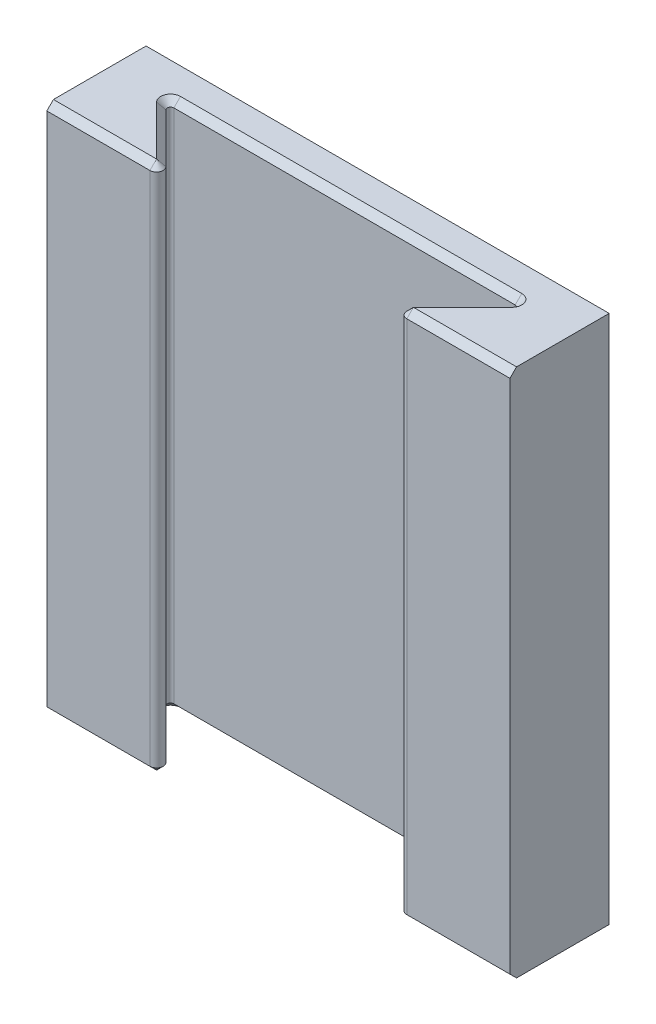
SolidWorks part; units mm, degrees
ref_plane "Top Plane" through (0, 0, 0) normal (0, 0, 1) x (1, 0, 0)
ref_plane "Front Plane" through (0, 0, 0) normal (0, 1, 0) x (1, 0, 0)
ref_plane "Right Plane" through (0, 0, 0) normal (1, 0, 0) x (0, 0, -1)
sketch "Sketch1" plane through (0, 0, 0) normal (0, 0, 1) x (1, 0, 0)
  line L1 (0, 0) -> (70, 0)
  line L2 (0, 0) -> (0, 80)
  line L3 (0, 80) -> (70, 80)
  line L4 (70, 0) -> (70, 80)
  dimension "D1" = 70
  dimension "D2" = 80
extrude "Boss-Extrude1" add sketch "Sketch1" along normal blind 15
sketch "Sketch2" plane through (0, 0, 0) normal (0, -1, 0) x (1, 0, 0)
  line L0 (18, 15) -> (8, 5)
  line L1 (0, 15) -> (70, 15) construction
  line L2 (8, 5) -> (62, 5)
  line L3 (62, 5) -> (52, 15)
  line L4 (52, 15) -> (18, 15)
  line L5 (0, 0) -> (70, 0) construction
  line L6 (70, 15) -> (70, 0) construction
  line L7 (0, 15) -> (0, 0) construction
  dimension "D1" = 45
  dimension "D2" = 45
  dimension "D3" = 5
  dimension "D4" = 8
  dimension "D5" = 8
extrude "Cut-Extrude1" cut sketch "Sketch2" against normal through all
sketch "Sketch3" plane through (0, 0, 15) normal (0, 0, 1) x (1, 0, 0)
  line L0 (0, 80) -> (0, 0) construction
  line L1 (18, 80) -> (0, 80) construction
  circle A0 centre (5, 75) radius 3.5
  dimension "D2" = 7
  dimension "D3" = 5
  dimension "D1" = 5
sketch "Sketch4" plane through (0, 0, 5) normal (0, 0, 1) x (1, 0, 0)
  line L0 (8, 80) -> (62, 80) construction
  line L1 (0, 80) -> (0, 0) construction
  circle A0 centre (47.5, 17.5) radius 3.5
  dimension "D1" = 7
  dimension "D3" = 47.5
  dimension "D2" = 62.5
fillet "Fillet1" radius 0.5 2 edges at (62, 40, 5) (8, 40, 5)
fillet "Fillet2" radius 1 2 edges at (52, 40, 15) (18, 40, 15)
ref_plane "Plane1" through (45, 0, 0) normal (-1, 0, 0) x (0, 0, 1)
chamfer "Chamfer1" distance 1 angle 45 18 edges at (7.7929, 80, 15) (62.2071, 80, 15) (16.5097, 80, 14.3827) (53.4903, 80, 14.3827) (12.5732, 80, 9.5732) (57.4268, 80, 9.5732) (8.7452, 80, 5.3087) (61.2548, 80, 5.3087) (35, 80, 5) (7.7929, 0, 15) (62.2071, 0, 15) (16.5097, 0, 14.3827) (53.4903, 0, 14.3827) (12.5732, 0, 9.5732) (57.4268, 0, 9.5732) (8.7452, 0, 5.3087) (61.2548, 0, 5.3087) (35, 0, 5)
